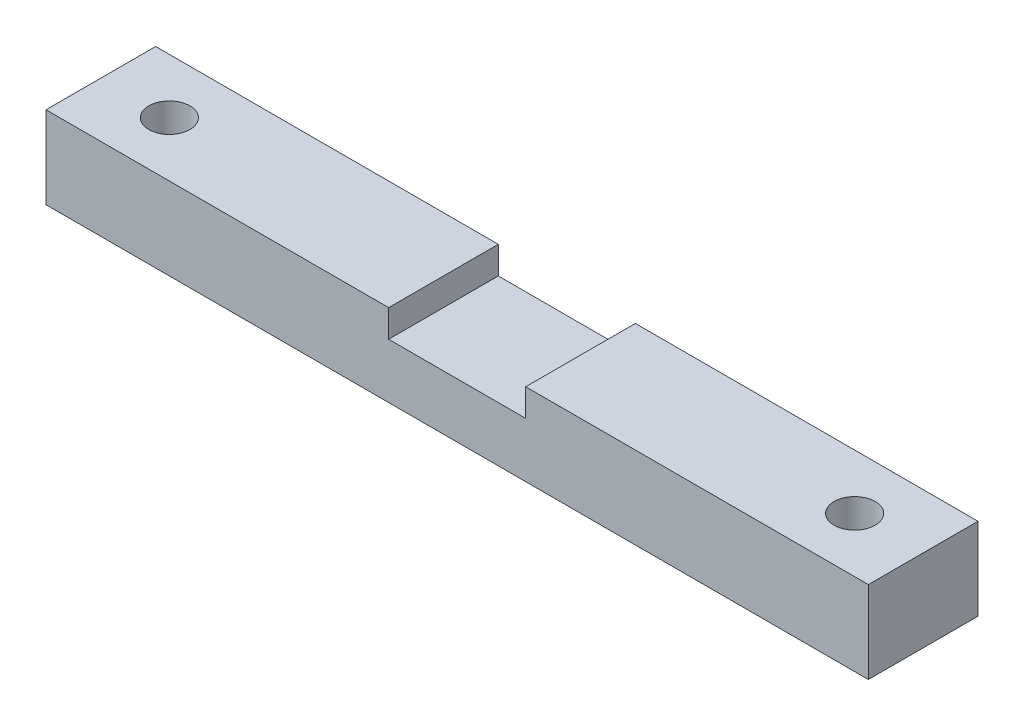
SolidWorks part; units mm, degrees
ref_plane "Front Plane" through (0, 0, 0) normal (0, 0, 1) x (1, 0, 0)
ref_plane "Top Plane" through (0, 0, 0) normal (0, 1, 0) x (1, 0, 0)
ref_plane "Right Plane" through (0, 0, 0) normal (1, 0, 0) x (0, 0, -1)
sketch "Sketch1" plane through (0, 0, 0) normal (0, 1, 0) x (1, 0, 0)
  line L1 (-30, -4) -> (30, -4)
  line L2 (-30, -4) -> (-30, 4)
  line L3 (-30, 4) -> (30, 4)
  line L4 (30, -4) -> (30, 4)
  line L5 (-30, -4) -> (30, 4) construction
  line L6 (-30, 4) -> (30, -4) construction
  point P0 (0, 0)
  dimension "D1" = 60
  dimension "D2" = 8
extrude "Boss-Extrude1" add sketch "Sketch1" along normal blind 6
sketch "Sketch2" plane through (0, 0, 4) normal (0, 0, 1) x (1, 0, 0)
  line L0 (-30, 6) -> (30, 6) construction
  line L1 (-5, 6) -> (5, 6)
  line L2 (-5, 6) -> (-5, 4)
  line L3 (-5, 4) -> (5, 4)
  line L4 (5, 6) -> (5, 4)
  point P4 (0, 6)
  point P7 (0, 6)
  dimension "D1" = 10
  dimension "D2" = 2
extrude "Cut-Extrude1" cut sketch "Sketch2" against normal through all
sketch "Sketch3" plane through (0, 6, 0) normal (0, 1, 0) x (1, 0, 0)
  line L0 (-30, 0) -> (30, 0) construction
  line L1 (-30, 4) -> (-30, -4) construction
  line L2 (30, -4) -> (30, 4) construction
  circle A0 centre (-25, 0) radius 1.5
  circle A1 centre (25, 0) radius 1.5
  dimension "D1" = 3
  dimension "D2" = 3
  dimension "D3" = 5
  dimension "D4" = 5
extrude "Cut-Extrude2" cut sketch "Sketch3" against normal through all
